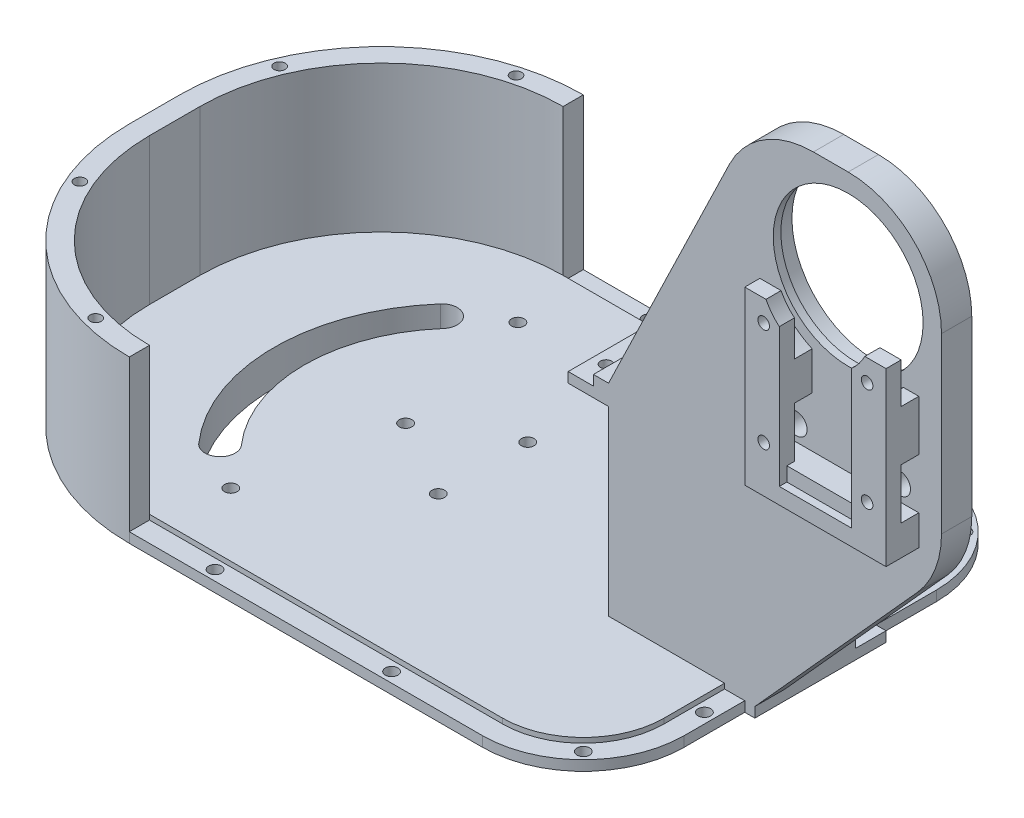
SolidWorks part; units mm, degrees
ref_plane "정면" through (0, 0, 0) normal (0, 0, 1) x (1, 0, 0)
ref_plane "윗면" through (0, 0, 0) normal (0, 1, 0) x (1, 0, 0)
ref_plane "우측면" through (0, 0, 0) normal (1, 0, 0) x (0, 0, -1)
sketch "스케치1" plane through (0, 0, 0) normal (0, 1, 0) x (1, 0, 0)
  circle A0 centre (0, 0) radius 40
  dimension "D1" = 80
extrude "보스-돌출1" add sketch "스케치1" along normal blind 4
sketch "스케치2" plane through (0, 0, 0) normal (0, -1, 0) x (1, 0, 0)
  line L0 (-22.5418, 33.0434) -> (-15.3511, 0)
  line L1 (-17.3456, 36.0434) -> (7.6755, 13.2944)
  line L2 (-22.5417, -33.0435) -> (-15.3511, 0)
  line L9 (-17.3456, -36.0435) -> (7.6755, -13.2944)
  line L10 (39.8873, -3) -> (7.6755, -13.2944)
  line L11 (39.8873, 3) -> (7.6755, 13.2944)
  arc A0 (-4.7504, -14.2279) -> (14.6969, -3) centre (0, 0) ccw construction
  arc A1 (-9.9465, 11.2279) -> (-9.9465, -11.2279) centre (0, 0) ccw construction
  arc A2 (-17.3456, 36.0434) -> (-22.5418, 33.0434) centre (0, 0) ccw
  arc A3 (14.6969, 3) -> (-4.7504, 14.2279) centre (0, 0) ccw construction
  arc A4 (39.8873, -3) -> (39.8873, 3) centre (0, 0) ccw
  arc A5 (-22.5417, -33.0435) -> (-17.3456, -36.0435) centre (0, 0) ccw
  point P14 (0, 0)
  dimension "D1" = 30
  dimension "D2" = 40
extrude "컷-돌출1" cut sketch "스케치2" against normal blind 2
sketch "스케치3" plane through (0, 4, 0) normal (0, 1, 0) x (1, 0, 0)
  line L1 (-60, 45) -> (70, 45)
  line L2 (-60, 45) -> (-60, -45)
  line L3 (-60, -45) -> (70, -45)
  line L4 (70, 45) -> (70, -45)
  line L5 (-60, 45) -> (70, -45) construction
  line L6 (-60, -45) -> (70, 45) construction
  circle A0 centre (0, 0) radius 40 construction
  point P0 (5, 0)
  dimension "D1" = 90
  dimension "D2" = 130
  dimension "D3" = 70
extrude "보스-돌출2" add sketch "스케치3" along normal blind 3
fillet "필렛1" radius 40 2 edges at (-60, 5.5, -45) (-60, 5.5, 45)
fillet "필렛2" radius 20 2 edges at (70, 5.5, 45) (70, 5.5, -45)
sketch "스케치6" plane through (0, 4, 0) normal (0, -1, 0) x (1, 0, 0)
  line L0 (68, 13) -> (72, 13)
  line L1 (68, -13) -> (72, -13)
  line L2 (50, -45) -> (-20, -45) construction
  line L11 (68, -13) -> (68, 13)
  line L28 (72, -13) -> (72, 13)
  dimension "D3" = 26
  dimension "D4" = 32
extrude "보스-돌출3" add sketch "스케치6" against normal blind 43
sketch "스케치7" plane through (0, 4, 0) normal (0, -1, 0) x (1, 0, 0)
  line L1 (-20, -45) -> (-20, -41)
  line L2 (-60, 5) -> (-60, -5)
  line L3 (-60, 5) -> (-60, -5)
  line L4 (-56, 5) -> (-56, -5)
  line L5 (-56, 5) -> (-56, -5)
  line L6 (-20, 41) -> (-20, 45)
  arc A8 (-60, -5) -> (-20, -45) centre (-20, -5) ccw
  arc A9 (-20, 45) -> (-60, 5) centre (-20, 5) ccw
  arc A10 (-60, -5) -> (-20, -45) centre (-20, -5) ccw
  arc A11 (-20, 45) -> (-60, 5) centre (-20, 5) ccw
  arc A12 (-56, -5) -> (-20, -41) centre (-20, -5) ccw
  arc A13 (-20, 41) -> (-56, 5) centre (-20, 5) ccw
  arc A14 (-56, -5) -> (-20, -41) centre (-20, -5) ccw
  arc A15 (-20, 41) -> (-56, 5) centre (-20, 5) ccw
  dimension "D1" = 0
  dimension "D2" = 4
extrude "보스-돌출4" add sketch "스케치7" against normal blind 32
sketch "스케치9" plane through (0, 0, 0) normal (0, -1, 0) x (1, 0, 0)
  arc A4 (-25, 22) -> (-25, -22) centre (0, 0) ccw construction
  arc A5 (-27.2521, 23.9819) -> (-27.2521, -23.9819) centre (0, 0) ccw
  arc A6 (-22.7479, 20.0181) -> (-22.7479, -20.0181) centre (0, 0) ccw
  arc A7 (-22.7479, 20.0181) -> (-27.2521, 23.9819) centre (-25, 22) ccw
  arc A8 (-27.2521, -23.9819) -> (-22.7479, -20.0181) centre (-25, -22) ccw
  circle A9 centre (0, 0) radius 40 construction
  point P16 (-33.3017, 0)
  dimension "D1" = 25
  dimension "D2" = 25
  dimension "D3" = 22
  dimension "D4" = 3
extrude "컷-돌출2" cut sketch "스케치9" against normal through all
sketch "스케치10" plane through (0, 7, 0) normal (0, 1, 0) x (1, 0, 0)
  line L0 (68, 13) -> (68, -13) construction
  line L1 (43, -7) -> (68, -7)
  line L2 (43, -7) -> (43, -13)
  line L3 (43, -13) -> (68, -13)
  line L4 (68, -7) -> (68, -13)
  arc A1 (-22.7479, 20.0181) -> (-22.7479, -20.0181) centre (0, 0) ccw construction
  dimension "D1" = 6
  dimension "D2" = 7
  dimension "D3" = 25
extrude "보스-돌출5" add sketch "스케치10" along normal blind 40
sketch "스케치11" plane through (0, 0, 7) normal (0, 0, -1) x (-1, 0, 0)
  line L0 (-109, 47) -> (-72, 6)
  line L3 (-72, 107) -> (-109, 107)
  line L4 (-109, 47) -> (-109, 107)
  line L5 (-43, 47) -> (-72, 6)
  line L6 (-72, 107) -> (-43, 47)
  line L7 (-68, 47) -> (-43, 47) construction
  line L9 (-72, 47) -> (-72, 4) construction
  line L10 (-70, 4) -> (-72, 4) construction
  point P0 (-72, 11.7817)
  dimension "D1" = 60
  dimension "D2" = 37
  dimension "D3" = 2
extrude "보스-돌출6" add sketch "스케치11" against normal blind 6
fillet "필렛3" radius 18.5 3 edges at (109, 47, 10) (72, 107, 10) (109, 107, 10)
sketch "스케치12" plane through (0, 7, 0) normal (0, 1, 0) x (1, 0, 0)
  line L0 (68, -7) -> (68, 13) construction
  line L1 (68, 7) -> (43, 7)
  line L2 (68, 7) -> (68, 13)
  line L3 (68, 13) -> (43, 13)
  line L4 (43, 7) -> (43, 13)
  line L5 (68, -7) -> (43, -7) construction
  dimension "D1" = 25
  dimension "D2" = 6
  dimension "D3" = 14
extrude "컷-돌출3" cut sketch "스케치12" against normal blind 1
sketch "스케치14" plane through (0, 47, 0) normal (0, 1, 0) x (1, 0, 0)
  line L0 (72, 13) -> (72, -7) construction
  line L1 (68, 7) -> (72, 7)
  line L2 (68, 7) -> (68, 13)
  line L3 (68, 13) -> (72, 13)
  line L4 (72, 7) -> (72, 13)
  line L5 (68, 13) -> (43, 13) construction
extrude "컷-돌출4" cut sketch "스케치14" against normal blind 41
sketch "스케치15" plane through (0, 0, 7) normal (0, 0, -1) x (-1, 0, 0)
  circle A0 centre (-90.5, 88.5) radius 16.15
  dimension "D1" = 32.3
extrude "컷-돌출5" cut sketch "스케치15" against normal blind 4.5
sketch "스케치16" plane through (0, 0, 11.5) normal (0, 0, -1) x (-1, 0, 0)
  circle A0 centre (-90.5, 88.5) radius 14.85
  circle A1 centre (-90.5, 88.5) radius 16.15 construction
  dimension "D1" = 1.3
extrude "컷-돌출6" cut sketch "스케치16" against normal through all
chamfer "모따기1" distance 1 angle 67 1 edges at (74.35, 88.5, 7)
sketch "스케치17" plane through (0, 7, 0) normal (0, 1, 0) x (1, 0, 0)
  line L26 (66, 13) -> (66, 25)
  line L27 (50, 41) -> (-20, 41)
  line L28 (66, 13) -> (66, 25)
  line L29 (50, 41) -> (-20, 41)
  line L30 (66, -25) -> (66, -13)
  line L31 (66, -25) -> (66, -13)
  line L33 (-20, -41) -> (50, -41)
  line L34 (-20, -41) -> (50, -41)
  arc A15 (66, 25) -> (50, 41) centre (50, 25) ccw
  arc A16 (66, 25) -> (50, 41) centre (50, 25) ccw
  arc A19 (50, -41) -> (66, -25) centre (50, -25) ccw
  arc A20 (50, -41) -> (66, -25) centre (50, -25) ccw
  dimension "D1" = 4
  dimension "D2" = 4
  dimension "D3" = 4
extrude "컷-돌출-얇게1" cut sketch "스케치17" against normal blind 1 thin
sketch "스케치18" plane through (0, 0, 13) normal (0, 0, 1) x (1, 0, 0)
  line L6 (76.5, 55.5) -> (104.5, 55.5)
  line L7 (76.5, 55.5) -> (76.5, 49.5)
  line L8 (76.5, 49.5) -> (104.5, 49.5)
  line L9 (104.5, 55.5) -> (104.5, 49.5)
  line L10 (76.5, 65.5) -> (83.35, 65.5)
  line L11 (76.5, 65.5) -> (76.5, 75.5)
  line L12 (76.5, 75.5) -> (79.5455, 75.5)
  line L13 (83.35, 65.5) -> (83.35, 73.0767)
  line L14 (104.5, 65.5) -> (97.65, 65.5)
  line L15 (104.5, 65.5) -> (104.5, 75.5)
  line L16 (104.5, 75.5) -> (101.4545, 75.5)
  line L17 (97.65, 65.5) -> (97.65, 73.0767)
  circle A1 centre (90.5, 88.5) radius 14.85 construction
  arc A2 (79.5455, 75.5) -> (83.35, 73.0767) centre (90.5, 88.5) ccw
  arc A3 (97.65, 73.0767) -> (101.4545, 75.5) centre (90.5, 88.5) ccw
  point P14 (83.35, 69.2884)
  dimension "D8" = 34
  dimension "D1" = 28
  dimension "D2" = 14
  dimension "D4" = 6
  dimension "D3" = 33
  dimension "D5" = 10
  dimension "D6" = 10
  dimension "D7" = 14.3
extrude "보스-돌출7" add sketch "스케치18" along normal blind 6.5
sketch "스케치19" plane through (0, 0, 19.5) normal (0, 0, 1) x (1, 0, 0)
  line L0 (104.5, 55.5) -> (76.5, 55.5) construction
  line L1 (83.35, 55.5) -> (97.65, 55.5)
  line L2 (83.35, 55.5) -> (83.35, 52.7)
  line L3 (83.35, 52.7) -> (97.65, 52.7)
  line L4 (97.65, 55.5) -> (97.65, 52.7)
  line L5 (76.5, 49.5) -> (104.5, 49.5) construction
  point P8 (97.65, 54.1)
  point P9 (90.5, 49.5)
  dimension "D1" = 3.2
  dimension "D2" = 14.3
  dimension "D3" = 7.15
extrude "컷-돌출7" cut sketch "스케치19" against normal blind 1.5
sketch "스케치20" plane through (0, 55.5, 0) normal (0, 1, 0) x (1, 0, 0)
  line L0 (83.35, -18) -> (83.35, -19.5) construction
  line L1 (104.5, -19.5) -> (97.65, -19.5)
  line L2 (104.5, -19.5) -> (104.5, -16.5)
  line L3 (104.5, -16.5) -> (97.65, -16.5)
  line L4 (97.65, -19.5) -> (97.65, -16.5)
  line L5 (76.5, -19.5) -> (83.35, -19.5)
  line L6 (76.5, -19.5) -> (76.5, -16.5)
  line L7 (76.5, -16.5) -> (83.35, -16.5)
  line L8 (83.35, -19.5) -> (83.35, -16.5)
  line L9 (97.65, -18) -> (97.65, -19.5) construction
  dimension "D1" = 3
extrude "보스-돌출8" add sketch "스케치20" along normal blind 28
sketch "스케치22" plane through (0, 0, 19.5) normal (0, 0, 1) x (1, 0, 0)
  line L1 (80.25, 79.2) -> (100.75, 79.2) construction
  line L2 (80.25, 79.2) -> (80.25, 58.7) construction
  line L3 (80.25, 58.7) -> (100.75, 58.7) construction
  line L4 (100.75, 79.2) -> (100.75, 58.7) construction
  line L5 (83.35, 52.7) -> (97.65, 52.7) construction
  circle A0 centre (90.5, 88.5) radius 14.85 construction
  circle A1 centre (80.25, 79.2) radius 1.15
  circle A2 centre (100.75, 79.2) radius 1.15
  circle A3 centre (80.25, 58.7) radius 1.15
  circle A4 centre (100.75, 58.7) radius 1.15
  dimension "D5" = 2.3
  dimension "D1" = 20.5
  dimension "D2" = 20.5
  dimension "D3" = 6
  dimension "D4" = 10.25
extrude "컷-돌출8" cut sketch "스케치22" against normal up to next
sketch "스케치23" plane through (0, 0, 7) normal (0, 0, -1) x (-1, 0, 0)
  circle A0 centre (-80.25, 58.7) radius 2.1
  circle A1 centre (-100.75, 58.7) radius 2.1
  dimension "D1" = 4.2
extrude "컷-돌출9" cut sketch "스케치23" against normal up to next
sketch "스케치24" plane through (0, 0, 19.5) normal (0, 0, 1) x (1, 0, 0)
  circle A0 centre (90.5, 88.5) radius 11
  dimension "D1" = 22
extrude "컷-돌출10" cut sketch "스케치24" against normal up to next
sketch "스케치25" plane through (0, 47, 0) normal (0, 1, 0) x (1, 0, 0)
  line L0 (43, -13) -> (66, -13) construction
  line L1 (43, 13) -> (35, 13)
  line L2 (72, 7) -> (72, -13)
  line L3 (72, -13) -> (35, -13)
  line L4 (35, 13) -> (35, -13)
  line L5 (66, 13) -> (43, 13) construction
  line L7 (43, -7) -> (43, -13) construction
  line L8 (43, 13) -> (43, 7)
  line L9 (43, 7) -> (72, 7)
  point P0 (0, 0)
  dimension "D1" = 8
extrude "보스-돌출9" add sketch "스케치25" against normal blind 4
sketch "스케치27" plane through (0, 47, 0) normal (0, 1, 0) x (1, 0, 0)
  line L1 (35, -13) -> (40, -13)
  line L2 (35, -13) -> (35, 13)
  line L3 (35, 13) -> (40, 13)
  line L4 (40, -13) -> (40, 13)
  line L5 (35, -13) -> (40, 13) construction
  line L6 (35, 13) -> (40, -13) construction
  line L7 (43, 13) -> (35, 13) construction
  point P4 (37.5, 0)
  dimension "D1" = 5
extrude "컷-돌출11" cut sketch "스케치27" against normal blind 2
sketch "스케치29" plane through (0, 43, 0) normal (0, -1, 0) x (1, 0, 0)
  line L0 (37.5, 13) -> (37.5, -13) construction
  line L1 (35, 13) -> (40, 13) construction
  line L2 (40, -13) -> (35, -13) construction
  circle A0 centre (37.5, 8) radius 1.85
  circle A1 centre (37.5, -8) radius 1.85
  dimension "D1" = 3.7
  dimension "D2" = 16
  dimension "D3" = 5
extrude "보스-돌출10" add sketch "스케치29" along normal blind 3
sketch "스케치28" plane through (0, 45, 0) normal (0, 1, 0) x (1, 0, 0)
  line L0 (37.5, 13) -> (37.5, -13) construction
  line L1 (40, 13) -> (35, 13) construction
  line L2 (35, -13) -> (40, -13) construction
  circle A0 centre (37.5, 8) radius 1.1
  circle A1 centre (37.5, -8) radius 1.1
  dimension "D2" = 5
  dimension "D3" = 2.2
  dimension "D1" = 16
extrude "컷-돌출12" cut sketch "스케치28" against normal up to next
sketch "스케치30" plane through (0, 36, 0) normal (0, 1, 0) x (1, 0, 0)
  line L6 (-20, -41) -> (-20, -45) construction
  line L7 (-58, 5) -> (-58, -5)
  line L8 (-58, 5) -> (-58, -5) construction
  line L9 (-20, 41) -> (-20, 45) construction
  circle A8 centre (-30, -41.6606) radius 1.1
  circle A9 centre (-30, 41.6606) radius 1.1
  arc A10 (-20, 43) -> (-58, 5) centre (-20, 5) ccw
  arc A11 (-58, -5) -> (-20, -43) centre (-20, -5) ccw
  arc A12 (-20, 43) -> (-58, 5) centre (-20, 5) ccw construction
  arc A13 (-58, -5) -> (-20, -43) centre (-20, -5) ccw construction
  circle A14 centre (-55, 19.7986) radius 1.1
  circle A15 centre (-55, -19.7986) radius 1.1
  point P10 (0, 0)
  point P11 (0, 0)
  dimension "D2" = 2.2
  dimension "D3" = 10
  dimension "D4" = 35
  dimension "D1" = 2
extrude "컷-돌출13" cut sketch "스케치30" against normal blind 10
sketch "스케치31" plane through (0, 4, 0) normal (0, -1, 0) x (1, 0, 0)
  line L10 (68, -13) -> (68, -25)
  line L11 (50, -43) -> (-20, -43)
  line L12 (68, -13) -> (68, -25) construction
  line L13 (50, -43) -> (-20, -43) construction
  line L18 (68, 25) -> (68, 13)
  line L19 (-20, 43) -> (50, 43)
  line L20 (68, 25) -> (68, 13) construction
  line L21 (-20, 43) -> (50, 43) construction
  line L22 (43, -10) -> (68, -10)
  line L23 (43, -10) -> (68, -10) construction
  arc A6 (50, -43) -> (68, -25) centre (50, -25) ccw
  arc A7 (50, -43) -> (68, -25) centre (50, -25) ccw construction
  circle A9 centre (-5, 43) radius 1.25
  arc A10 (68, 25) -> (50, 43) centre (50, 25) ccw
  arc A11 (68, 25) -> (50, 43) centre (50, 25) ccw construction
  circle A12 centre (30, 43) radius 1.25
  circle A13 centre (30, -43) radius 1.25
  circle A14 centre (-5, -43) radius 1.25
  circle A15 centre (68, -19) radius 1.25
  circle A16 centre (68, 19) radius 1.25
  circle A17 centre (62.7279, 37.7279) radius 1.25
  circle A18 centre (62.7279, -37.7279) radius 1.25
  circle A19 centre (48, -10) radius 1.25
  circle A20 centre (65.5, -10) radius 1.25
  dimension "D4" = 2.5
  dimension "D5" = 35
  dimension "D6" = 15
  dimension "D7" = 17.5
  dimension "D8" = 5
  dimension "D9" = 2.5
  dimension "D1" = 2
  dimension "D2" = 2
  dimension "D3" = 3
extrude "컷-돌출14" cut sketch "스케치31" against normal up to next
sketch "스케치32" plane through (0, 0, -7) normal (0, 0, -1) x (-1, 0, 0)
  line L2 (-70, 6) -> (-70, 47)
  line L3 (-70, 6) -> (-70, 47) construction
  line L4 (-43, 43) -> (-43, 47) construction
  line L5 (-43, 45) -> (-72, 45)
  line L6 (-43, 45) -> (-72, 45) construction
  line L7 (-72, 47) -> (-43, 47) construction
  circle A0 centre (-53, 45) radius 1.1
  circle A1 centre (-70, 35) radius 1.1
  circle A2 centre (-70, 15) radius 1.1
  dimension "D3" = 2.2
  dimension "D4" = 10
  dimension "D5" = 12
  dimension "D6" = 20
  dimension "D1" = 2
  dimension "D2" = 2
extrude "컷-돌출15" cut sketch "스케치32" against normal blind 8
sketch "스케치33" plane through (0, 2, 0) normal (0, -1, 0) x (1, 0, 0)
  line L12 (32.8496, 0) -> (5.117, 8.8629)
  line L13 (5.117, 8.8629) -> (-16.4249, 28.4486)
  line L14 (-16.4249, 28.4486) -> (-10.234, 0)
  line L15 (-10.234, 0) -> (-16.4248, -28.4486)
  line L16 (-16.4248, -28.4486) -> (5.117, -8.8629)
  line L17 (5.117, -8.8629) -> (32.8496, 0)
  line L18 (32.8496, 0) -> (5.117, 8.8629) construction
  line L19 (5.117, 8.8629) -> (-16.4249, 28.4486) construction
  line L20 (-16.4249, 28.4486) -> (-10.234, 0) construction
  line L21 (-10.234, 0) -> (-16.4248, -28.4486) construction
  line L22 (-16.4248, -28.4486) -> (5.117, -8.8629) construction
  line L23 (5.117, -8.8629) -> (32.8496, 0) construction
  circle A3 centre (-16.4249, 28.4486) radius 1.25
  circle A4 centre (32.8496, 0) radius 1.25
  circle A5 centre (-16.4248, -28.4486) radius 1.25
  circle A6 centre (-10.234, 0) radius 1.25
  circle A7 centre (5.117, 8.8629) radius 1.25
  circle A8 centre (5.117, -8.8629) radius 1.25
  dimension "D2" = 2.5
  dimension "D1" = 5
extrude "컷-돌출16" cut sketch "스케치33" against normal through all
